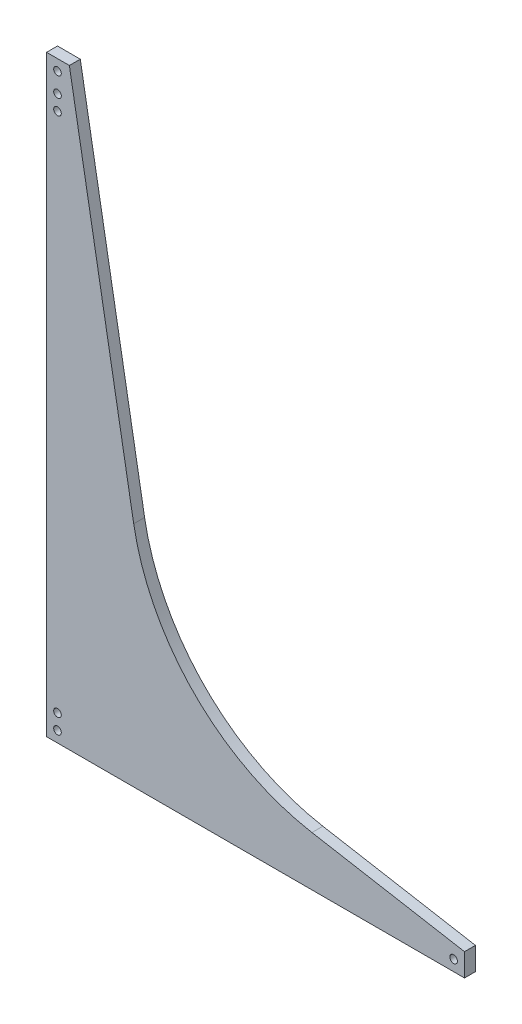
SolidWorks part; units mm, degrees
material "Maple"
ref_plane "Front Plane" through (0, 0, 0) normal (0, 0, 1) x (1, 0, 0)
ref_plane "Top Plane" through (0, 0, 0) normal (0, 1, 0) x (1, 0, 0)
ref_plane "Right Plane" through (0, 0, 0) normal (1, 0, 0) x (0, 0, -1)
sketch "Sketch1" plane through (0, 0, 0) normal (0, 0, 1) x (1, 0, 0)
  line L0 (0, 0) -> (698.5, 0)
  line L1 (0, 0) -> (0, 990.6)
  line L2 (0, 990.6) -> (38.1, 990.6)
  line L4 (698.5, 0) -> (698.5, 38.1)
  line L5 (698.5, 38.1) -> (443.531, 83.0579)
  line L11 (38.1, 990.6) -> (145.5889, 381)
  arc A0 (443.531, 83.0579) -> (145.5889, 381) centre (507.3127, 444.7817) cw
  dimension "D1" = 990.6
  dimension "D2" = 698.5
  dimension "D3" = 38.1
  dimension "D4" = 38.1
  dimension "D5" = 100
  dimension "D6" = 609.6
  dimension "D7" = 100
extrude "Boss-Extrude1" add sketch "Sketch1" along normal mid plane 18.2562
sketch "Sketch2" plane through (0, 0, 9.1281) normal (0, 0, 1) x (1, 0, 0)
  line L0 (0, 990.6) -> (0, 0) construction
  line L1 (38.1, 990.6) -> (0, 990.6) construction
  line L2 (0, 0) -> (698.5, 0) construction
  line L3 (698.5, 0) -> (698.5, 38.1) construction
  line L6 (0, 990.6) -> (0, 0) construction
  line L7 (38.1, 990.6) -> (0, 990.6) construction
  circle A0 centre (18.2562, 972.3438) radius 6.35
  circle A1 centre (18.2562, 18.2562) radius 6.35
  circle A2 centre (680.2438, 18.2562) radius 6.35
  circle A4 centre (18.2562, 43.6562) radius 6.35
  circle A5 centre (18.2562, 939.8) radius 6.35
  circle A6 centre (18.2562, 914.4) radius 6.35
  point P22 (0, 0)
  point P25 (18.2562, 939.8)
  dimension "D2" = 12.7
  dimension "D4" = 12.7
  dimension "D9" = 12.7
  dimension "D10" = 12.7
  dimension "D13" = 12.7
  dimension "D14" = 12.7
  dimension "D15" = 25.4
  dimension "D16" = 18.2562
  dimension "D17" = 50.8
  dimension "D18" = 18.2562
  dimension "D1" = 18.2562
  dimension "D3" = 18.2562
  dimension "D5" = 18.2562
  dimension "D6" = 18.2562
  dimension "D7" = 18.2562
  dimension "D8" = 18.2562
  dimension "D11" = 25.4
  dimension "D12" = 18.2562
extrude "Cut-Extrude1" cut sketch "Sketch2" against normal through all
